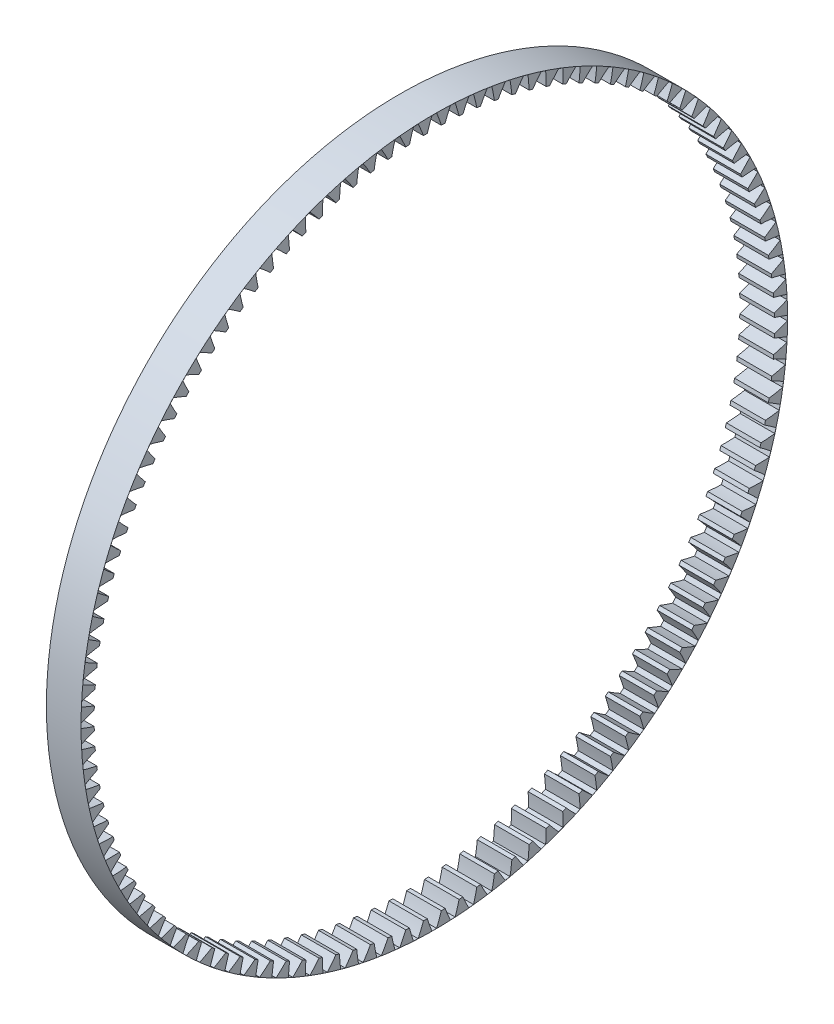
SolidWorks part; units mm, degrees
ref_plane "Plane1" through (0, 0, 0) normal (0, 0, 1) x (1, 0, 0)
ref_plane "Plane2" through (0, 0, 0) normal (0, 1, 0) x (1, 0, 0)
ref_plane "Plane3" through (0, 0, 0) normal (1, 0, 0) x (0, 0, -1)
other "Configuration Table"
sketch "HoldingSke" plane through (0, 0, 0) normal (0, 1, 0) x (1, 0, 0)
  line L0 (0, 0) -> (-0.5, -0.866)
  line L1 (-15, 0) -> (100, 0) construction
  line L2 (0, 0) -> (-2.1039, 2.3779)
  line L3 (0, 0) -> (-11.863, 4.5341)
  line L4 (0, 0) -> (-4.318, 7.479)
  line L5 (0, 0) -> (-23.7986, -8.8762)
  line L6 (0, 0) -> (-10.5278, -7.1032)
  line L7 (-2.1039, 2.3779) -> (3.3635, 27.1825)
  line L8 (-76.2, 3.3779) -> (-54.61, 3.3779)
  line L9 (-71.009, 38.7566) -> (-53.1078, 45.2721)
  line L10 (-76.2, 71.12) -> (104.1128, 71.12)
  line L11 (0, 0) -> (-6, 0)
  line L12 (-76.2, 101.6) -> (-76.162, 101.6)
  line L13 (24.9733, 27.94) -> (52.9518, 28.4284)
  line L14 (24.9733, 27.94) -> (24.9743, 27.94)
  line L15 (24.9733, 27.94) -> (100.4006, 29.5858)
  circle A0 centre (0, 0) radius 18
  circle A1 centre (0, 0) radius 12.7
  circle A2 centre (0, 0) radius 12.7
  dimension "Num_teeth" = 120
  dimension "Pitch_radius" = 180.3128
  dimension "Width" = 6
sketch "BasProSke" plane through (0, 0, 0) normal (0, 1, 0) x (1, 0, 0)
  line L0 (-10, 0) -> (60, 0) construction
  line L1 (0, 59) -> (0, 61.2764)
  line L2 (0, 59) -> (6, 59)
  line L3 (6, 59) -> (6, 61.2764)
  line L4 (6, 61.2764) -> (0, 61.2764)
  dimension "Thickness" = 6
  dimension "Diameter" = 122.5528
revolve "Base-Revolve" add sketch "BasProSke" angle 360 about L0
sketch "TooCutSke" plane through (0, 0, 0) normal (1, 0, 0) x (0, 0, -1)
  line L3 (0.8804, 59.9935) -> (0.8804, 53.6633) construction
  line L4 (0, 0) -> (0, 59.563) construction
  line L5 (0, 0) -> (-1.7886, 68.3041) construction
  line L6 (-27.4212, 50.0427) -> (36.5015, 51.7166) construction
  circle A0 centre (0, 0) radius 60 construction
  circle A1 centre (0, 0) radius 61.251 construction
  circle A2 centre (0, 0) radius 50.7434 construction
  circle A3 centre (0, 0) radius 58.9746 construction
  arc A4 (1.2222, 58.9619) -> (0.4069, 61.2496) centre (-27.4212, 50.0427) ccw
  arc A5 (1.2222, 58.9619) -> (-1.2222, 58.9619) centre (0, 0) ccw
  arc A6 (0.4069, 61.2496) -> (-0.4069, 61.2496) centre (0, 0) ccw
  arc A7 (-0.4069, 61.2496) -> (-1.2222, 58.9619) centre (27.4212, 50.0427) ccw
extrude "ToothCut" cut sketch "TooCutSke" along normal through all
fillet "Breaks" [suppressed] radius 0.1
fillet "RootFillets" [suppressed] radius 0.251
pattern_circular "TeethCuts" count 120 every 3 about axis through (-10, 0, 0) along (1, 0, 0) of "RootFillets", "Breaks", "ToothCut"
equation "' \"Module@HoldingSke\" = 6.35"
equation "' \"Num_teeth@HoldingSke\" = 24"
equation "' \"Ap@HoldingSke\" =  14.5"
equation "' \"Ap@HoldingSke\" = 14.5"
equation "' \"Width@HoldingSke\" = 12"
equation "' \"Diameter@HoldingSke\" = 8 * 25.4"
equation "' \"Show_teeth@HoldingSke\" = 100"
equation "' \"Backlash@HoldingSke\" = 0.009 * 25.4"
equation "' \"Addendum_fac@HoldingSke\" = 1.0"
equation "' \"Dedendum_fac@HoldingSke\" = 1.25"
equation "' \"Dedendum_add@HoldingSke\" = 0.00005 * 25.4"
equation "' \"Clearance_fac@HoldingSke\" = 0.25"
equation "\"Pitch@HoldingSke\" = 1 / \"Module@HoldingSke\" "
equation "\"Overcut_dia@TooCutSke\" = (\"Num_teeth@HoldingSke\" - 2 * \"Addendum_fac@HoldingSke\") / \"Pitch@HoldingSke\" - 0.002 * 25.4"
equation "\"Pitch_dia@TooCutSke\" = \"Num_teeth@HoldingSke\" / \"Pitch@HoldingSke\""
equation "\"Base_dia@TooCutSke\" = \"Num_teeth@HoldingSke\" / \"Pitch@HoldingSke\" * cos((\"Ap@HoldingSke\"  * 3.14159265 / 180)) * 0.90"
equation "\"Root_dia@TooCutSke\" = \"Num_teeth@HoldingSke\"  / \"Pitch@HoldingSke\" + 2 *  \"Dedendum_fac@HoldingSke\"/ \"Pitch@HoldingSke\" + \"Dedendum_add@HoldingSke\" * 2"
equation "\"Half_ang@TooCutSke\" = 180 / \"Num_teeth@HoldingSke\""
equation "\"Half_CT@TooCutSke\" = \"Num_teeth@HoldingSke\" / \"Pitch@HoldingSke\" * sin((3.14159265 / 2 / \"Num_teeth@HoldingSke\")) / 2 + 10 * \"Backlash@HoldingSke\" / 4"
equation "\"Flank_rad@TooCutSke\" = \"Num_teeth@HoldingSke\" / \"Pitch@HoldingSke\" / 4"
equation "\"Radius@RootFillets\"= \"Clearance_fac@HoldingSke\" / \"Pitch@HoldingSke\" + \"Dedendum_add@HoldingSke\""
equation "\"Break_rad@Breaks\" = 0.02 / \"Pitch@HoldingSke\" * 5"
equation "\"Num_teeth@TeethCuts\" = int( \"Show_teeth@HoldingSke\" ) + 1"
equation "\"Num_teeth@TeethCuts\" = ((sgn( \"Num_teeth@TeethCuts\" - \"Num_teeth@HoldingSke\" )-1)*( \"Num_teeth@TeethCuts\" - \"Num_teeth@HoldingSke\" ))/-2+ \"Num_teeth@HoldingSke\""
equation "\"Num_teeth@TeethCuts\" = ((sgn( \"Num_teeth@TeethCuts\" - 2.0)+1)*( \"Num_teeth@TeethCuts\" - 2.0))/2 +2.0"
equation "\"Angle@TeethCuts\" = 360.0 / \"Num_teeth@HoldingSke\""
equation "\"Diameter@BasProSke\" = \"Num_teeth@HoldingSke\"  / \"Pitch@HoldingSke\" + 2 *  \"Dedendum_fac@HoldingSke\"/ \"Pitch@HoldingSke\" + \"Dedendum_add@HoldingSke\" * 2 + 0.002 * 25.4"
equation "\"Diameter@BasProSke\" = ((sgn( \"Diameter@BasProSke\"  - \"Diameter@HoldingSke\" )+1)*( \"Diameter@BasProSke\"  - \"Diameter@HoldingSke\" ))/2 + \"Diameter@HoldingSke\""
equation "\"Inside_diameter@BasProSke\" =  (\"Num_teeth@HoldingSke\" - 2 * \"Addendum_fac@HoldingSke\") / \"Pitch@HoldingSke\" "
equation "\"Thickness@BasProSke\"  = \"Width@HoldingSke\""
